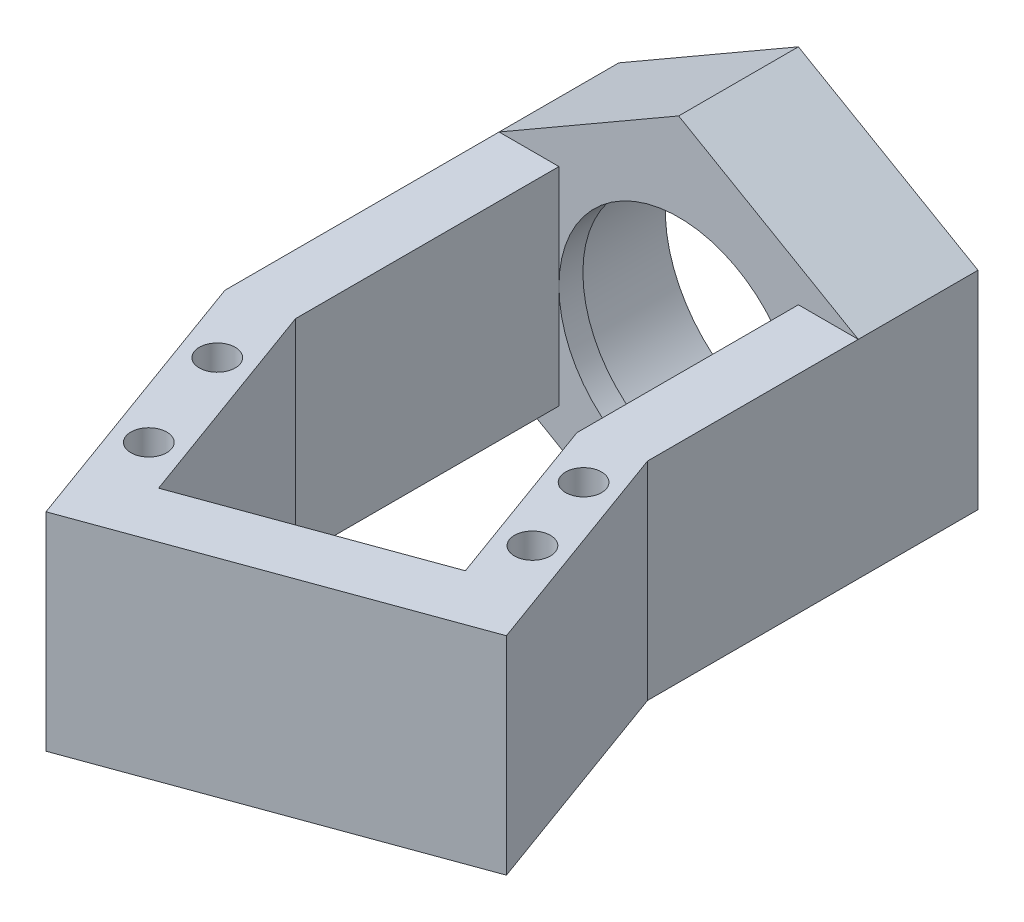
SolidWorks part; units mm, degrees
ref_plane "Front Plane" through (0, 0, 0) normal (0, 0, 1) x (1, 0, 0)
ref_plane "Top Plane" through (0, 0, 0) normal (0, 1, 0) x (1, 0, 0)
ref_plane "Right Plane" through (0, 0, 0) normal (1, 0, 0) x (0, 0, -1)
sketch "Sketch1" plane through (0, 0, 0) normal (0, 0, 1) x (1, 0, 0)
  line L1 (0, 17.3205) -> (-15, 8.6603)
  line L2 (-15, 8.6603) -> (-15, -8.6603)
  line L3 (-15, -8.6603) -> (0, -17.3205)
  line L4 (0, -17.3205) -> (15, -8.6603)
  line L5 (15, -8.6603) -> (15, 8.6603)
  line L6 (15, 8.6603) -> (0, 17.3205)
  circle A0 centre (0, 0) radius 11.125
  circle A1 centre (0, 0) radius 15 construction
  dimension "D1" = 22.25
  dimension "D2" = 30
extrude "Boss-Extrude2" add sketch "Sketch1" along normal blind 8
sketch "Sketch2" plane through (0, 0, 8) normal (0, 0, 1) x (1, 0, 0)
  line L0 (15, 8.6603) -> (0, 17.3205) construction
  line L1 (0, 17.3205) -> (-15, 8.6603)
  line L2 (-15, 8.6603) -> (-15, -8.6603)
  line L3 (-15, -8.6603) -> (0, -17.3205)
  line L4 (0, -17.3205) -> (15, -8.6603)
  line L5 (15, -8.6603) -> (15, 8.6603)
  line L6 (15, 8.6603) -> (0, 17.3205)
  circle A0 centre (0, 0) radius 15 construction
  circle A1 centre (0, 0) radius 10
  dimension "D1" = 20
extrude "Boss-Extrude3" add sketch "Sketch2" along normal blind 2
sketch "Sketch6" plane through (0, 0, 0) normal (0, 1, 0) x (1, 0, 0)
  line L0 (15, -10) -> (15, -27.6)
  line L1 (15, -27.6) -> (20.0345, -41.4321)
  line L2 (20.0345, -41.4321) -> (15.3301, -43.1443)
  line L3 (15.3301, -43.1443) -> (10, -28.5)
  line L4 (10, -28.5) -> (10, -10)
  line L5 (15, -10) -> (0, -10) construction
  line L6 (10, -10) -> (15, -10)
  line L7 (-15, -10) -> (-15, -32.9)
  line L8 (-15, -32.9) -> (-8.1596, -51.6939)
  line L9 (-8.1596, -51.6939) -> (-3.4552, -49.9816)
  line L10 (-3.4552, -49.9816) -> (-10, -32)
  line L11 (-10, -32) -> (-10, -10)
  line L12 (0, -10) -> (-15, -10) construction
  line L13 (-10, -10) -> (-15, -10)
  line L14 (-3.4552, -49.9816) -> (20.0345, -41.4321) construction
  point P18 (20.1463, -41.4056)
  dimension "D1" = 160
  dimension "D2" = 17.6
  dimension "D3" = 18.5
  dimension "D4" = 5
  dimension "D6" = 5
  dimension "D7" = 160
  dimension "D8" = 20
  dimension "D9" = 22.9
  dimension "D10" = 22
extrude "Boss-Extrude6" add sketch "Sketch6" against normal up to vertex (8.6603 mm away) and the other way blind 8.66 up to point (15, -8.6603, 10)
sketch "Sketch8" plane through (0, -8.6603, 0) normal (0, -1, 0) x (1, 0, 0)
  line L0 (-5.8074, 50.8377) -> (-12.5, 32.45) construction
  line L1 (-8.1596, 51.6939) -> (-3.4552, 49.9816) construction
  line L2 (-15, 32.9) -> (-10, 32) construction
  line L3 (10, 28.5) -> (15, 27.6) construction
  line L4 (17.6823, 42.2882) -> (12.5, 28.05) construction
  line L5 (15.3301, 43.1443) -> (20.0345, 41.4321) construction
  circle A0 centre (-10.4479, 38.0882) radius 1.5
  circle A1 centre (-7.1755, 47.079) radius 1.5
  circle A2 centre (16.3142, 38.5294) radius 1.5
  circle A3 centre (13.8681, 31.8088) radius 1.5
  dimension "D1" = 3
  dimension "D2" = 3
  dimension "D5" = 3
  dimension "D7" = 3
  dimension "D3" = 4
  dimension "D4" = 6
  dimension "D6" = 4
  dimension "D8" = 4
extrude "Cut-Extrude2" cut sketch "Sketch8" against normal through all both and the other way through all
sketch "Sketch9" plane through (15.6596, 0, 43.0244) normal (0.342, 0, 0.9397) x (0.9397, 0, -0.342)
  line L0 (-25.3479, 8.66) -> (4.6556, 8.66)
  line L1 (4.6556, 8.66) -> (4.6556, -8.6603)
  line L2 (4.6556, -8.6603) -> (-25.3479, -8.6603)
  line L3 (-25.3479, -8.6603) -> (-25.3479, 8.66)
extrude "Boss-Extrude7" add sketch "Sketch9" along normal blind 5
